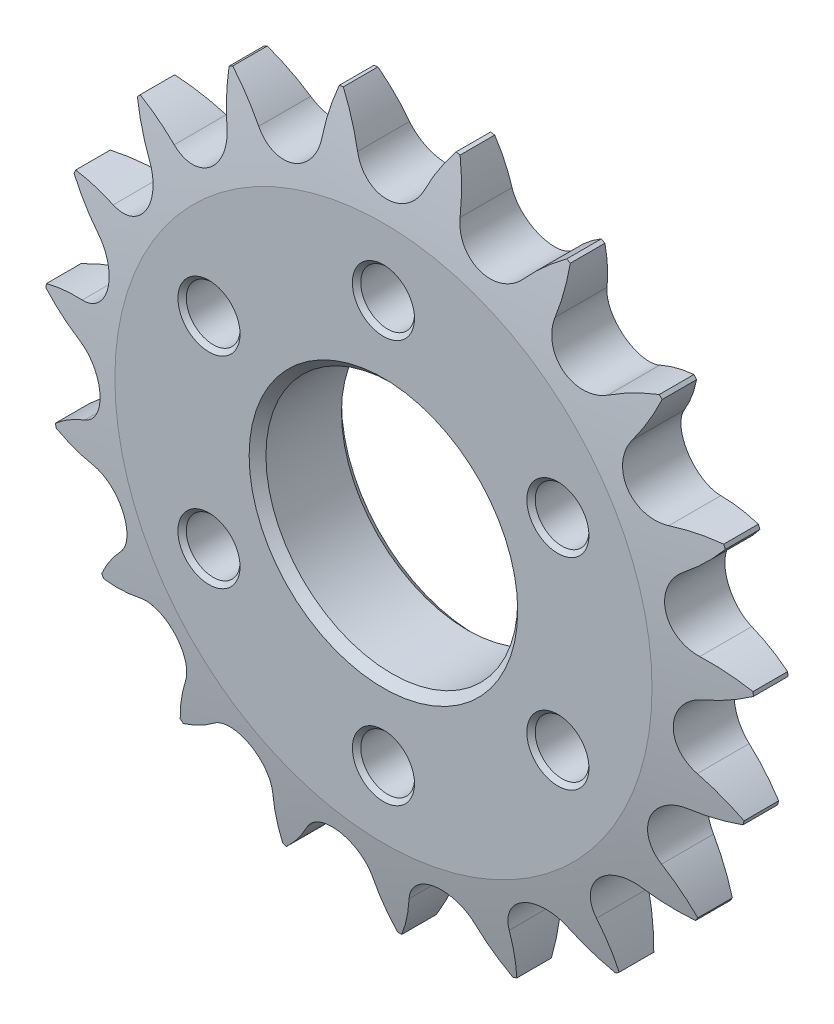
SolidWorks part; units mm, degrees
material "1.7033 (34Cr4)"
ref_plane "Спереди" through (0, 0, 0) normal (0, 0, 1) x (1, 0, 0)
ref_plane "Сверху" through (0, 0, 0) normal (0, 1, 0) x (1, 0, 0)
ref_plane "Справа" through (0, 0, 0) normal (1, 0, 0) x (0, 0, -1)
sketch "Эскиз2" plane through (0, 0, 0) normal (0, 0, 1) x (1, 0, 0)
  line L0 (20.3293, 37.0514) -> (19.8992, 37.2842)
  line L1 (31.2584, 28.443) -> (30.9271, 28.8028)
  line L2 (38.8001, 16.7523) -> (38.6037, 17.2002)
  line L3 (42.1373, 3.2462) -> (42.0969, 3.7336)
  line L4 (40.9082, -10.6116) -> (41.0283, -10.1375)
  line L5 (35.2461, -23.3195) -> (35.5136, -22.9101)
  line L6 (25.7645, -33.5004) -> (26.1505, -33.2)
  line L7 (13.491, -40.051) -> (13.9535, -39.8922)
  line L8 (-0.2445, -42.2614) -> (0.2445, -42.2614)
  line L9 (-13.9535, -39.8922) -> (-13.491, -40.051)
  line L10 (-26.1505, -33.2) -> (-25.7645, -33.5004)
  line L11 (-35.5136, -22.9101) -> (-35.2461, -23.3195)
  line L12 (-41.0283, -10.1375) -> (-40.9082, -10.6116)
  line L13 (-42.0969, 3.7336) -> (-42.1373, 3.2462)
  line L14 (-38.6037, 17.2002) -> (-38.8001, 16.7523)
  line L15 (-30.9271, 28.8028) -> (-31.2584, 28.443)
  line L16 (-19.8992, 37.2842) -> (-20.3293, 37.0514)
  line L17 (-6.7148, 41.7253) -> (-7.1972, 41.6448)
  line L18 (7.1972, 41.6448) -> (6.7148, 41.7253)
  circle A0 centre (0, 0) radius 15
  arc A9 (8.2299, 36.2324) -> (15.7599, 33.6474) centre (12.5268, 36.4893) ccw
  arc A10 (19.8992, 37.2842) -> (15.7599, 33.6474) centre (31.867, 19.4891) ccw
  arc A11 (19.5486, 31.597) -> (20.3293, 37.0514) centre (-1.114, 37.3375) ccw
  arc A12 (19.5486, 31.597) -> (25.8313, 26.707) centre (23.6961, 30.4448) ccw
  arc A13 (30.9271, 28.8028) -> (25.8313, 26.707) centre (36.4684, 8.0859) ccw
  arc A14 (28.7489, 23.5376) -> (31.2584, 28.443) centre (11.0698, 35.6762) ccw
  arc A15 (28.7489, 23.5376) -> (33.1034, 16.8726) centre (32.2976, 21.1011) ccw
  arc A16 (38.6037, 17.2002) -> (33.1034, 16.8726) centre (37.118, -4.1935) ccw
  arc A17 (34.8339, 12.9275) -> (38.8001, 16.7523) centre (22.054, 30.1488) ccw
  arc A18 (34.8339, 12.9275) -> (36.7883, 5.2097) centre (37.3991, 9.4707) ccw
  arc A19 (42.0969, 3.7336) -> (36.7883, 5.2097) centre (33.7452, -16.0185) ccw
  arc A20 (37.144, 0.9165) -> (42.1373, 3.2462) centre (30.6484, 21.3543) ccw
  arc A21 (37.144, 0.9165) -> (36.4866, -7.0177) centre (38.4479, -3.1859) ccw
  arc A22 (41.0283, -10.1375) -> (36.4866, -7.0177) centre (26.7156, -26.1076) ccw
  arc A23 (35.4291, -11.1938) -> (40.9082, -10.6116) centre (35.9215, 10.2457) ccw
  arc A24 (35.4291, -11.1938) -> (32.231, -18.4846) centre (35.3302, -15.4973) ccw
  arc A25 (35.5136, -22.9101) -> (32.231, -18.4846) centre (16.7909, -33.3676) ccw
  arc A26 (29.8748, -22.0911) -> (35.2461, -23.3195) centre (37.302, -1.9731) ccw
  arc A27 (29.8748, -22.0911) -> (24.4827, -27.9485) centre (28.384, -26.1293) ccw
  arc A28 (26.1505, -33.2) -> (24.4827, -27.9485) centre (5.0467, -37.0116) ccw
  arc A29 (21.0831, -30.5945) -> (25.7645, -33.5004) centre (34.6402, -13.9781) ccw
  arc A30 (21.0831, -30.5945) -> (14.0813, -34.3837) centre (18.3619, -33.9298) ccw
  arc A31 (13.9535, -39.8922) -> (14.0813, -34.3837) centre (-7.2444, -36.6449) ccw
  arc A32 (10.0068, -35.7824) -> (13.491, -40.051) centre (28.2246, -24.4684) ccw
  arc A33 (10.0068, -35.7824) -> (2.154, -37.0928) centre (6.35, -38.0535) ccw
  arc A34 (0.2445, -42.2614) -> (2.154, -37.0928) centre (-18.7504, -32.3071) ccw
  arc A35 (-2.154, -37.0928) -> (-0.2445, -42.2614) centre (18.7504, -32.3071) ccw
  arc A36 (-2.154, -37.0928) -> (-10.0068, -35.7824) centre (-6.35, -38.0535) ccw
  arc A37 (-13.491, -40.051) -> (-10.0068, -35.7824) centre (-28.2246, -24.4684) ccw
  arc A38 (-14.0813, -34.3837) -> (-13.9535, -39.8922) centre (7.2444, -36.6449) ccw
  arc A39 (-14.0813, -34.3837) -> (-21.0831, -30.5945) centre (-18.3619, -33.9298) ccw
  arc A40 (-25.7645, -33.5004) -> (-21.0831, -30.5945) centre (-34.6402, -13.9781) ccw
  arc A41 (-24.4827, -27.9485) -> (-26.1505, -33.2) centre (-5.0467, -37.0116) ccw
  arc A42 (-24.4827, -27.9485) -> (-29.8748, -22.0911) centre (-28.384, -26.1293) ccw
  arc A43 (-35.2461, -23.3195) -> (-29.8748, -22.0911) centre (-37.302, -1.9731) ccw
  arc A44 (-32.231, -18.4846) -> (-35.5136, -22.9101) centre (-16.7909, -33.3676) ccw
  arc A45 (-32.231, -18.4846) -> (-35.4291, -11.1938) centre (-35.3302, -15.4973) ccw
  arc A46 (-40.9082, -10.6116) -> (-35.4291, -11.1938) centre (-35.9215, 10.2457) ccw
  arc A47 (-36.4866, -7.0177) -> (-41.0283, -10.1375) centre (-26.7156, -26.1076) ccw
  arc A48 (-36.4866, -7.0177) -> (-37.144, 0.9165) centre (-38.4479, -3.1859) ccw
  arc A49 (-42.1373, 3.2462) -> (-37.144, 0.9165) centre (-30.6484, 21.3543) ccw
  arc A50 (-36.7883, 5.2097) -> (-42.0969, 3.7336) centre (-33.7452, -16.0185) ccw
  arc A51 (-36.7883, 5.2097) -> (-34.8339, 12.9275) centre (-37.3991, 9.4707) ccw
  arc A52 (-38.8001, 16.7523) -> (-34.8339, 12.9275) centre (-22.054, 30.1488) ccw
  arc A53 (-33.1034, 16.8726) -> (-38.6037, 17.2002) centre (-37.118, -4.1935) ccw
  arc A54 (-33.1034, 16.8726) -> (-28.7489, 23.5376) centre (-32.2976, 21.1011) ccw
  arc A55 (-31.2584, 28.443) -> (-28.7489, 23.5376) centre (-11.0698, 35.6762) ccw
  arc A56 (-25.8313, 26.707) -> (-30.9271, 28.8028) centre (-36.4684, 8.0859) ccw
  arc A57 (-25.8313, 26.707) -> (-19.5486, 31.597) centre (-23.6961, 30.4448) ccw
  arc A58 (-20.3293, 37.0514) -> (-19.5486, 31.597) centre (1.114, 37.3375) ccw
  arc A59 (-15.7599, 33.6474) -> (-19.8992, 37.2842) centre (-31.867, 19.4891) ccw
  arc A60 (-15.7599, 33.6474) -> (-8.2299, 36.2324) centre (-12.5268, 36.4893) ccw
  arc A61 (-7.1972, 41.6448) -> (-8.2299, 36.2324) centre (13.1771, 34.9527) ccw
  arc A62 (-3.9807, 36.9415) -> (-6.7148, 41.7253) centre (-23.8123, 28.7803) ccw
  arc A63 (-3.9807, 36.9415) -> (3.9807, 36.9415) centre (0, 38.5796) ccw
  arc A64 (6.7148, 41.7253) -> (3.9807, 36.9415) centre (23.8123, 28.7803) ccw
  arc A65 (8.2299, 36.2324) -> (7.1972, 41.6448) centre (-13.1771, 34.9527) ccw
  dimension "D1" = 30
extrude "Бобышка-Вытянуть2" add sketch "Эскиз2" along normal mid plane 8
sketch "Эскиз3" plane through (0, 0, 4) normal (0, 0, 1) x (1, 0, 0)
  circle A0 centre (0, 0) radius 24 construction
  circle A1 centre (0, 24) radius 3.2
  circle A2 centre (20.7846, 12) radius 3.2
  circle A3 centre (20.7846, -12) radius 3.2
  circle A4 centre (0, -24) radius 3.2
  circle A5 centre (-20.7846, -12) radius 3.2
  circle A6 centre (-20.7846, 12) radius 3.2
  point P17 (0, 0)
  dimension "D1" = 48
  dimension "D2" = 6.4
  dimension "D3" = 6
extrude "Вырез-Вытянуть1" cut sketch "Эскиз3" against normal blind 38
sketch "Эскиз6" plane through (0, 0, 4) normal (0, 0, 1) x (1, 0, 0)
  point P0 (0, 24)
  point P3 (-20.7846, 12)
  point P6 (-20.7846, -12)
  point P9 (0, -24)
  point P12 (20.7846, -12)
  point P15 (20.7846, 12)
hole_wizard "Отверстие с зазором M61" positions "Эскиз6" profile "Эскиз5" hole size "M6" standard "DIN" end condition through all
sketch "Эскиз5" plane through (0, 24, 4) normal (1, 0, 0) x (0, -1, 0)
  line L0 (0, 0) -> (0, 8)
  line L1 (0, 8) -> (3.2, 8)
  line L2 (3.2, 8) -> (3.2, 0.5)
  line L3 (3.2, 0.5) -> (3.7, 0)
  line L5 (3.7, 0) -> (0, 0)
  line L6 (-3.2, 0.5) -> (-3.7, 0) construction
  line L11 (0, -6.35) -> (0, 107.95) construction
  dimension "Диаметр сквозного отверстия" = 6.4
  dimension "Глубина сквозного отверстия" = 8
  dimension "Диаметр передней зенковки" = 7.4
  dimension "Угол передней зенковки" = 90
sketch "Эскиз7" plane through (0, 0, 0) normal (0, 1, 0) x (1, 0, 0)
  line L0 (-47, -0.9757) -> (-47, -4)
  line L1 (-32, -4) -> (-1036.8482, -4) construction
  line L2 (-3.7, -4) -> (3.7, -4) construction
  line L3 (-32, -4) -> (-47, -4)
  line L4 (0, 0) -> (0, -12.4689) construction
  arc A0 (-47, -0.9757) -> (-32, -4) centre (0, 193.4234) ccw
  dimension "D1" = 400
  dimension "D2" = 15
  dimension "D3" = 32
revolve "Вырез-Повернуть1" cut sketch "Эскиз7" angle 360 about L4
mirror "Зеркальное отражение1" about plane through (0, 0, 0) normal (0, 0, 1) of "Вырез-Повернуть1"
sketch "Эскиз8" plane through (0, 0, -4) normal (0, 0, -1) x (-1, 0, 0)
  circle A0 centre (0, 0) radius 15
  circle A1 centre (0, 0) radius 18
  dimension "D1" = 36
  dimension "D2" = 30
extrude "Бобышка-Вытянуть3" add sketch "Эскиз8" along normal blind 3
chamfer "Фаска1" distance 1 angle 45 2 edges at (15, 0, 4) (-15, 0, -7)
